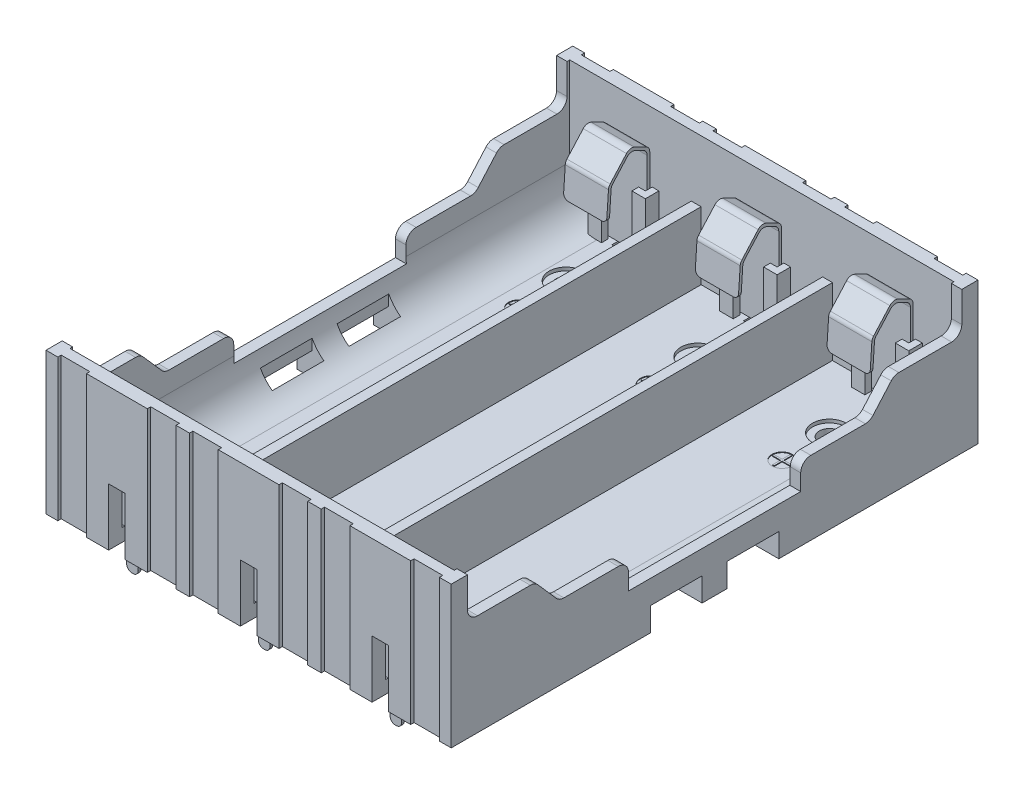
SolidWorks part; units mm, degrees
material "ABS"
ref_plane "Спереди" through (0, 0, 0) normal (0, 0, 1) x (1, 0, 0)
ref_plane "Сверху" through (0, 0, 0) normal (0, 1, 0) x (1, 0, 0)
ref_plane "Справа" through (0, 0, 0) normal (1, 0, 0) x (0, 0, -1)
other "Configuration Table"
sketch "Эскиз1" plane through (0, 0, 0) normal (0, 1, 0) x (1, 0, 0)
  line L1 (-30, 39) -> (30, 39)
  line L2 (-30, 39) -> (-30, -39)
  line L3 (-30, -39) -> (30, -39)
  line L4 (30, 39) -> (30, -39)
  line L5 (-30, 39) -> (30, -39) construction
  line L6 (-30, -39) -> (30, 39) construction
  point P0 (0, 0)
  dimension "D1" = 78
  dimension "D2" = 60
extrude "Основа" add sketch "Эскиз1" along normal blind 21
sketch "Эскиз2" plane through (0, 0, 0) normal (0, 1, 0) x (1, 0, 0)
  line L1 (30, 39) -> (-30, 39) construction
  line L2 (-4.5, 39) -> (-4.5, 38.5)
  line L3 (-4.5, 38.5) -> (-8.75, 38.5)
  line L4 (-8.75, 38.5) -> (-8.75, 39)
  line L5 (-8.75, 39) -> (-10.75, 39)
  line L6 (-10.75, 39) -> (-10.75, 38.5)
  line L7 (-10.75, 38.5) -> (-15, 38.5)
  line L8 (-15, 38.5) -> (-15, 39)
  line L9 (-15, 39) -> (-24, 39)
  line L10 (-24, 39) -> (-24, 38.5)
  line L11 (-24, 38.5) -> (-28.25, 38.5)
  line L12 (-28.25, 38.5) -> (-28.25, 39)
  line L13 (-28.25, 39) -> (-30, 39)
  line L14 (-30, 39) -> (-30, 49.7572)
  line L15 (-30, 49.7572) -> (30, 49.7572)
  line L16 (0, 49.7572) -> (0, 39)
  line L17 (4.5, 39) -> (-4.5, 39)
  line L18 (30, 39) -> (30, 49.7572)
  line L19 (15, 39) -> (24, 39)
  line L20 (24, 39) -> (24, 38.5)
  line L21 (28.25, 38.5) -> (28.25, 39)
  line L22 (24, 38.5) -> (28.25, 38.5)
  line L23 (28.25, 39) -> (30, 39)
  line L24 (15, 38.5) -> (15, 39)
  line L25 (10.75, 38.5) -> (15, 38.5)
  line L26 (10.75, 39) -> (10.75, 38.5)
  line L27 (8.75, 39) -> (10.75, 39)
  line L28 (4.5, 39) -> (4.5, 38.5)
  line L29 (4.5, 38.5) -> (8.75, 38.5)
  line L30 (8.75, 38.5) -> (8.75, 39)
  point P22 (0, 39)
  dimension "D1" = 9
  dimension "D2" = 2
  dimension "D3" = 4.25
  dimension "D4" = 0.5
extrude "Рёбра" cut sketch "Эскиз2" along normal through all contours L29 L30 L27 L26 L25 L24 L19 L20 L22 L21 L23 L18 L15 L16 L17 L28 | L17 L16 L15 L14 L13 L12 L11 L10 L9 L8 L7 L6 L5 L4 L3 L2 region at (-15.004, 0, -44.2695) region at (15.004, 0, -44.2695)
mirror "Зеркальное отражение1" about plane through (0, 0, 0) normal (0, 0, 1) of "Рёбра"
sketch "Эскиз3" plane through (0, 21, 0) normal (0, 1, 0) x (1, 0, 0)
  line L0 (19.45, 0) -> (-19.45, 0) construction
  line L1 (9, 37) -> (-9, 37)
  line L2 (9, 37) -> (9, -37)
  line L3 (9, -37) -> (-9, -37)
  line L4 (-9, 37) -> (-9, -37)
  line L5 (9, 37) -> (-9, -37) construction
  line L6 (9, -37) -> (-9, 37) construction
  line L8 (-28.45, 37) -> (-10.45, 37)
  line L9 (-28.45, 37) -> (-28.45, -37)
  line L10 (-28.45, -37) -> (-10.45, -37)
  line L11 (-10.45, 37) -> (-10.45, -37)
  line L12 (-28.45, 37) -> (-10.45, -37) construction
  line L13 (-28.45, -37) -> (-10.45, 37) construction
  line L15 (28.45, 37) -> (10.45, 37)
  line L16 (28.45, 37) -> (28.45, -37)
  line L17 (28.45, -37) -> (10.45, -37)
  line L18 (10.45, 37) -> (10.45, -37)
  line L19 (28.45, 37) -> (10.45, -37) construction
  line L20 (28.45, -37) -> (10.45, 37) construction
  point P0 (0, 0)
  point P9 (0, 0)
  dimension "D1" = 18
  dimension "D2" = 74
  dimension "D3" = 1.45
extrude "Отсеки" cut sketch "Эскиз3" against normal blind 19.1
fillet "Скругление1" radius 6 2 edges at (28.45, 1.9, 0) (-28.45, 1.9, 0)
sketch "Эскиз4" plane through (0, 0, 0) normal (1, 0, 0) x (0, 0, -1)
  line L0 (37, 21) -> (-37, 21) construction
  line L1 (37, 30.1) -> (-37, 30.1)
  line L2 (37, 30.1) -> (37, 11.9)
  line L3 (37, 11.9) -> (-37, 11.9)
  line L4 (-37, 30.1) -> (-37, 11.9)
  line L5 (37, 30.1) -> (-37, 11.9) construction
  line L6 (37, 11.9) -> (-37, 30.1) construction
  line L7 (-37, 1.9) -> (-37, 21) construction
  line L8 (37, 1.9) -> (-37, 1.9) construction
  point P0 (0, 21)
  dimension "D1" = 10
extrude "Уменьшение внутренних стенок" cut sketch "Эскиз4" against normal blind 15 and the other way blind 15
sketch "Эскиз5" plane through (30, 0, 0) normal (1, 0, 0) x (0, 0, -1)
  line L0 (-39, 21) -> (-36.6, 21)
  line L1 (-39, 21) -> (39, 21) construction
  line L2 (-36.6, 21) -> (-36.6, 15)
  line L3 (-36.6, 15) -> (-26.6, 15)
  line L4 (-26.6, 15) -> (-23, 10.9)
  line L5 (-23, 10.9) -> (-12.75, 10.9)
  line L6 (-12.75, 10.9) -> (-12.75, 7)
  line L7 (-12.75, 7) -> (12.75, 7)
  line L8 (0, 7) -> (0, 0) construction
  line L9 (-36.6, 21) -> (36.6, 21)
  line L10 (12.75, 10.9) -> (12.75, 7)
  line L11 (23, 10.9) -> (12.75, 10.9)
  line L12 (26.6, 15) -> (23, 10.9)
  line L13 (36.6, 15) -> (26.6, 15)
  line L14 (36.6, 21) -> (36.6, 15)
  point P20 (0, 21)
  line M12 (39, 21) -> (-39, 21)
  dimension "D1" = 12.75
  dimension "D2" = 10.25
  dimension "D3" = 2.4
  dimension "D4" = 10
  dimension "D5" = 6
  dimension "D6" = 3.9
  dimension "D7" = 7
extrude "Уменьшение внешних стенок" cut sketch "Эскиз5" against normal blind 15 contours L14 L2 L3 L4 L5 L6 L7 L10 L11 L12 L13 M12 region at (30, 15.4166, 0)
fillet "Скругление2" radius 1.5 8 edges at (29.225, 15, -36.6) (29.225, 15, -26.6) (29.225, 10.9, -23) (29.225, 10.9, -12.75) (29.225, 10.9, 12.75) (29.225, 10.9, 23) (29.225, 15, 26.6) (29.225, 15, 36.6)
mirror "Зеркальное отражение2" about plane through (0, 0, 0) normal (1, 0, 0) of "Скругление2", "Уменьшение внешних стенок"
sketch "Эскиз6" plane through (0, 0, 0) normal (0, 1, 0) x (1, 0, 0)
  line L0 (-4.5, -39) -> (4.5, -39) construction
  line L1 (-1.225, -42.5) -> (1.225, -42.5)
  line L2 (-1.225, -42.5) -> (-1.225, -35.5)
  line L3 (-1.225, -35.5) -> (1.225, -35.5)
  line L4 (1.225, -42.5) -> (1.225, -35.5)
  line L5 (-1.225, -42.5) -> (1.225, -35.5) construction
  line L6 (-1.225, -35.5) -> (1.225, -42.5) construction
  line L7 (-30, 0) -> (30, 0) construction
  line L8 (30, -39) -> (30, 39) construction
  line L9 (-24, -39) -> (-15, -39) construction
  line L10 (-20.725, -42.5) -> (-18.275, -42.5)
  line L11 (-20.725, -42.5) -> (-20.725, -35.5)
  line L12 (-20.725, -35.5) -> (-18.275, -35.5)
  line L13 (-18.275, -42.5) -> (-18.275, -35.5)
  line L14 (-20.725, -42.5) -> (-18.275, -35.5) construction
  line L15 (-20.725, -35.5) -> (-18.275, -42.5) construction
  line L16 (15, -39) -> (24, -39) construction
  line L17 (20.725, -42.5) -> (18.275, -42.5)
  line L18 (20.725, -42.5) -> (20.725, -35.5)
  line L19 (20.725, -35.5) -> (18.275, -35.5)
  line L20 (18.275, -42.5) -> (18.275, -35.5)
  line L21 (20.725, -42.5) -> (18.275, -35.5) construction
  line L22 (20.725, -35.5) -> (18.275, -42.5) construction
  line L23 (20.725, 35.5) -> (18.275, 42.5) construction
  line L24 (20.725, 42.5) -> (18.275, 35.5) construction
  line L25 (-20.725, 35.5) -> (-18.275, 42.5) construction
  line L26 (-20.725, 42.5) -> (-18.275, 35.5) construction
  line L27 (-1.225, 35.5) -> (1.225, 42.5) construction
  line L28 (-1.225, 42.5) -> (1.225, 35.5) construction
  line L29 (18.275, 42.5) -> (18.275, 35.5)
  line L30 (20.725, 35.5) -> (18.275, 35.5)
  line L31 (20.725, 42.5) -> (20.725, 35.5)
  line L32 (20.725, 42.5) -> (18.275, 42.5)
  line L33 (-18.275, 42.5) -> (-18.275, 35.5)
  line L34 (-20.725, 35.5) -> (-18.275, 35.5)
  line L35 (-20.725, 42.5) -> (-20.725, 35.5)
  line L36 (-20.725, 42.5) -> (-18.275, 42.5)
  line L37 (1.225, 42.5) -> (1.225, 35.5)
  line L38 (-1.225, 35.5) -> (1.225, 35.5)
  line L39 (-1.225, 42.5) -> (-1.225, 35.5)
  line L40 (-1.225, 42.5) -> (1.225, 42.5)
  point P0 (0, -39)
  point P7 (-19.5, -39)
  point P13 (0, 0)
  point P21 (19.5, -39)
  point P40 (19.5, 39)
  point P41 (-19.5, 39)
  point P42 (0, 39)
  dimension "D1" = 2.45
  dimension "D2" = 3.5
extrude "Вырезы под контакты" cut sketch "Эскиз6" along normal blind 8.5
sketch "Эскиз7" plane through (0, 0, 0) normal (0, 1, 0) x (1, 0, 0)
  line L0 (0, -35.5) -> (0, 35.5) construction
  line L1 (1.225, -35.5) -> (-1.225, -35.5) construction
  line L2 (-1.225, 35.5) -> (1.225, 35.5) construction
  line L3 (0, 0) -> (-26.025, 0) construction
  line L4 (-26.025, -23.825) -> (-26.025, 23.825) construction
  line L5 (-24, -38.5) -> (-28.25, -38.5) construction
  line L6 (-24.325, -10.8) -> (-27.725, -10.8)
  line L7 (-24.325, -10.8) -> (-24.325, -36.85)
  line L8 (-24.325, -36.85) -> (-27.725, -36.85)
  line L9 (-27.725, -10.8) -> (-27.725, -36.85)
  line L10 (-24.325, -10.8) -> (-27.725, -36.85) construction
  line L11 (-24.325, -36.85) -> (-27.725, -10.8) construction
  line L12 (-24.325, 10.8) -> (-27.725, 10.8)
  line L13 (-24.325, 10.8) -> (-24.325, 36.85)
  line L14 (-24.325, 36.85) -> (-27.725, 36.85)
  line L15 (-27.725, 10.8) -> (-27.725, 36.85)
  line L16 (-24.325, 10.8) -> (-27.725, 36.85) construction
  line L17 (-24.325, 36.85) -> (-27.725, 10.8) construction
  line L18 (-27.725, -1.375) -> (-24.325, -1.375)
  line L19 (-27.725, -1.375) -> (-27.725, 1.375)
  line L20 (-27.725, 1.375) -> (-24.325, 1.375)
  line L21 (-24.325, -1.375) -> (-24.325, 1.375)
  line L22 (-27.725, -1.375) -> (-24.325, 1.375) construction
  line L23 (-27.725, 1.375) -> (-24.325, -1.375) construction
  line L24 (24.325, 36.85) -> (27.725, 36.85)
  line L25 (24.325, 10.8) -> (24.325, 36.85)
  line L26 (27.725, 10.8) -> (27.725, 36.85)
  line L27 (24.325, 10.8) -> (27.725, 10.8)
  line L28 (24.325, -10.8) -> (27.725, -10.8)
  line L29 (24.325, -10.8) -> (24.325, -36.85)
  line L30 (27.725, -10.8) -> (27.725, -36.85)
  line L31 (24.325, -36.85) -> (27.725, -36.85)
  line L32 (27.725, -1.375) -> (27.725, 1.375)
  line L33 (27.725, -1.375) -> (24.325, -1.375)
  line L34 (24.325, -1.375) -> (24.325, 1.375)
  line L35 (27.725, 1.375) -> (24.325, 1.375)
  point P11 (-26.025, 0)
  dimension "D1" = 21.6
  dimension "D2" = 3.4
  dimension "D3" = 2.75
  dimension "D4" = 24.325
  dimension "D5" = 1.65
extrude "Пазы снизу" cut sketch "Эскиз7" along normal blind 1
sketch "Эскиз8" plane through (0, 0, 0) normal (0, 0, 1) x (1, 0, 0)
  line L0 (24.325, 1) -> (27.725, 1)
  line L1 (27.725, 1) -> (27.725, 3.073)
  arc A0 (24.325, 1) -> (27.725, 3.073) centre (22.45, 7.9) ccw
  arc A1 (22.45, 1.9) -> (28.45, 7.9) centre (22.45, 7.9) ccw construction
  arc A2 (22.45, 1.9) -> (28.45, 7.9) centre (22.45, 7.9) ccw construction
extrude "Вырез-Вытянуть9" cut sketch "Эскиз8" against normal up to surface and the other way up to surface up to face at (26.025, 0.5, -1.375) other way up to face at (26.025, 0.5, 1.375)
extrude "Вырез-Вытянуть10" cut sketch "Эскиз8<3>" along direction (0, 0, 1) on the side against the normal up to surface (36.85 mm away) from surface contours A0 L0 L1 region at (26.7298, 1.6233, 0) up to face at (26.025, 0.5, -36.85) starting at face at (26.025, 0.5, -10.8)
sketch "Эскиз8<3>" plane through (0, 0, 0) normal (0, 0, 1) x (1, 0, 0) same geometry as "Эскиз8"
extrude "Вырез-Вытянуть11" cut sketch "Эскиз8<4>" along normal up to surface (36.85 mm away) from surface up to face at (26.025, 0.5, 36.85) starting at face at (26.025, 0.5, 10.8)
sketch "Эскиз8<4>" plane through (0, 0, 0) normal (0, 0, 1) x (1, 0, 0) same geometry as "Эскиз8"
mirror "Зеркальное отражение3" about plane through (0, 0, 0) normal (1, 0, 0) of "Вырез-Вытянуть11", "Вырез-Вытянуть10", "Вырез-Вытянуть9"
sketch "Эскиз9" plane through (0, 0, 0) normal (0, 1, 0) x (1, 0, 0)
  line L0 (-30, 39) -> (-30, -39) construction
  line L1 (-34, -9.5) -> (-26, -9.5)
  line L2 (-34, -9.5) -> (-34, -1.85)
  line L3 (-34, -1.85) -> (-26, -1.85)
  line L4 (-26, -9.5) -> (-26, -1.85)
  line L5 (-34, -9.5) -> (-26, -1.85) construction
  line L6 (-34, -1.85) -> (-26, -9.5) construction
  line L7 (0, 0) -> (-30, 0) construction
  line L8 (-34, 1.85) -> (-26, 1.85)
  line L9 (-34, 1.85) -> (-34, 9.5)
  line L10 (-34, 9.5) -> (-26, 9.5)
  line L11 (-26, 1.85) -> (-26, 9.5)
  line L12 (-34, 1.85) -> (-26, 9.5) construction
  line L13 (-34, 9.5) -> (-26, 1.85) construction
  line L14 (-30, 0) -> (-30, 5.675) construction
  line L15 (-30, 0) -> (-30, -5.675) construction
  line L16 (0, 0) -> (0, -8.7492) construction
  line L17 (30, 0) -> (30, -5.675) construction
  line L18 (30, 0) -> (30, 5.675) construction
  line L19 (34, 9.5) -> (26, 1.85) construction
  line L20 (34, 1.85) -> (26, 9.5) construction
  line L21 (34, -1.85) -> (26, -9.5) construction
  line L22 (34, -9.5) -> (26, -1.85) construction
  line L23 (26, 1.85) -> (26, 9.5)
  line L24 (34, 9.5) -> (26, 9.5)
  line L25 (34, 1.85) -> (34, 9.5)
  line L26 (34, 1.85) -> (26, 1.85)
  line L27 (26, -9.5) -> (26, -1.85)
  line L28 (34, -1.85) -> (26, -1.85)
  line L29 (34, -9.5) -> (34, -1.85)
  line L30 (34, -9.5) -> (26, -9.5)
  point P0 (-30, -5.675)
  point P7 (-30, 5.675)
  point P29 (30, 5.675)
  point P30 (30, -5.675)
  dimension "D1" = 7.65
  dimension "D2" = 4
  dimension "D3" = 3.7
extrude "Пазы сбоку" cut sketch "Эскиз9" along normal blind 3.5
sketch "Эскиз10" plane through (0, 0, 0) normal (0, 1, 0) x (1, 0, 0)
  line L2 (-26, -9.5) -> (-26, -1.85) construction
  line L3 (-26, 1.85) -> (-26, 9.5) construction
  line L4 (0, 0) -> (0, -13.336) construction
  line L5 (27.75, 1.85) -> (26, 1.85)
  line L6 (-26, -9.5) -> (-26, -1.85)
  line L7 (-26, 1.85) -> (-26, 9.5)
  line L8 (-26, -1.85) -> (-27.75, -1.85)
  line L9 (-26, -1.85) -> (-30, -1.85) construction
  line L10 (-27.75, -1.85) -> (-27.75, -9.5)
  line L11 (-30, -9.5) -> (-26, -9.5) construction
  line L12 (-27.75, -9.5) -> (-26, -9.5)
  line L13 (-26, 9.5) -> (-27.75, 9.5)
  line L14 (-26.5292, 9.5) -> (-30, 9.5) construction
  line L15 (-27.75, 9.5) -> (-27.75, 1.85)
  line L16 (-30, 1.85) -> (-26, 1.85) construction
  line L17 (-27.75, 1.85) -> (-26, 1.85)
  line L18 (27.75, 9.5) -> (27.75, 1.85)
  line L19 (26, 9.5) -> (27.75, 9.5)
  line L20 (27.75, -9.5) -> (26, -9.5)
  line L21 (27.75, -1.85) -> (27.75, -9.5)
  line L22 (26, -1.85) -> (27.75, -1.85)
  line L23 (26, 1.85) -> (26, 9.5)
  line L24 (26, -9.5) -> (26, -1.85)
  dimension "D1" = 1.75
extrude "Вырез-Вытянуть15" cut sketch "Эскиз10" along normal through all
sketch "Эскиз11" plane through (0, 0, 0) normal (0, 1, 0) x (1, 0, 0)
  line L0 (-19.5, 35.5) -> (-19.5, 27.5) construction
  line L1 (19.5, -27.5) -> (-19.5, -27.5) construction
  line L2 (19.5, -27.5) -> (19.5, 27.5) construction
  line L3 (19.5, 27.5) -> (-19.5, 27.5) construction
  line L4 (-19.5, -27.5) -> (-19.5, 27.5) construction
  line L5 (19.5, -27.5) -> (-19.5, 27.5) construction
  line L6 (19.5, 27.5) -> (-19.5, -27.5) construction
  line L7 (-18.275, 35.5) -> (-20.725, 35.5) construction
  circle A0 centre (-19.5, 27.5) radius 1.5
  circle A1 centre (0, 27.5) radius 1.5
  circle A2 centre (19.5, 27.5) radius 1.5
  circle A3 centre (19.5, -27.5) radius 1.5
  circle A4 centre (0, -27.5) radius 1.5
  circle A5 centre (-19.5, -27.5) radius 1.5
  point P0 (0, 0)
  dimension "D2" = 3
  dimension "D1" = 55
extrude "Крепежные отверстия" cut sketch "Эскиз11" along normal through all
sketch "Эскиз12" plane through (0, 0, 0) normal (0, 1, 0) x (1, 0, 0)
  circle A0 centre (-19.5, 27.5) radius 1.5 construction
  circle A1 centre (0, 27.5) radius 1.5 construction
  circle A2 centre (19.5, 27.5) radius 1.5 construction
  circle A3 centre (19.5, -27.5) radius 1.5 construction
  circle A4 centre (0, -27.5) radius 1.5 construction
  circle A5 centre (-19.5, -27.5) radius 1.5 construction
  circle A6 centre (-19.5, 27.5) radius 1.5
  circle A7 centre (0, 27.5) radius 1.5
  circle A8 centre (19.5, 27.5) radius 1.5
  circle A9 centre (19.5, -27.5) radius 1.5
  circle A10 centre (0, -27.5) radius 1.5
  circle A11 centre (-19.5, -27.5) radius 1.5
  circle A12 centre (-19.5, 27.5) radius 2.8
  circle A13 centre (0, 27.5) radius 2.8
  circle A14 centre (19.5, 27.5) radius 2.8
  circle A15 centre (19.5, -27.5) radius 2.8
  circle A16 centre (0, -27.5) radius 2.8
  circle A17 centre (-19.5, -27.5) radius 2.8
  dimension "D1" = 1.3
extrude "Юбки отверстий" add sketch "Эскиз12" against normal blind 0.3
sketch "Эскиз13" plane through (0, 1.9, 0) normal (0, 1, 0) x (1, 0, 0)
  circle A0 centre (-19.5, -27.5) radius 1.5 construction
  circle A1 centre (0, -27.5) radius 1.5 construction
  circle A2 centre (19.5, 27.5) radius 1.5 construction
  circle A3 centre (0, 27.5) radius 1.5 construction
  circle A4 centre (-19.5, 27.5) radius 1.5 construction
  circle A5 centre (-19.5, -27.5) radius 1.5
  circle A6 centre (0, -27.5) radius 1.5
  circle A7 centre (19.5, 27.5) radius 1.5
  circle A8 centre (0, 27.5) radius 1.5
  circle A9 centre (-19.5, 27.5) radius 1.5
  circle A10 centre (19.5, -27.5) radius 1.5 construction
  circle A11 centre (19.5, -27.5) radius 1.5
  circle A12 centre (-19.5, -27.5) radius 2.5
  circle A13 centre (0, -27.5) radius 2.5
  circle A14 centre (19.5, 27.5) radius 2.5
  circle A15 centre (0, 27.5) radius 2.5
  circle A16 centre (-19.5, 27.5) radius 2.5
  circle A17 centre (19.5, -27.5) radius 2.5
  dimension "D1" = 1
extrude "Вырез-Вытянуть17" cut sketch "Эскиз13" against normal blind 0.5
sketch "Эскиз14" plane through (0, 1.9, 0) normal (0, 1, 0) x (1, 0, 0)
  line L0 (-19.5, 20.5) -> (-19.5, 27.5) construction
  line L1 (19.5, -20.5) -> (-19.5, -20.5) construction
  line L2 (19.5, -20.5) -> (19.5, 20.5) construction
  line L3 (19.5, 20.5) -> (-19.5, 20.5) construction
  line L4 (-19.5, -20.5) -> (-19.5, 20.5) construction
  line L5 (19.5, -20.5) -> (-19.5, 20.5) construction
  line L6 (19.5, 20.5) -> (-19.5, -20.5) construction
  line L7 (0.125, -19.2) -> (-0.125, -19.2)
  line L8 (-19.375, -19.2) -> (-19.625, -19.2)
  line L9 (-19.375, -19.2) -> (-19.375, -21.8)
  line L10 (-19.375, -21.8) -> (-19.625, -21.8)
  line L11 (-19.625, -19.2) -> (-19.625, -21.8)
  line L12 (-19.375, -19.2) -> (-19.625, -21.8) construction
  line L13 (-19.375, -21.8) -> (-19.625, -19.2) construction
  line L14 (-19.375, 21.8) -> (-19.625, 21.8)
  line L15 (-19.375, 21.8) -> (-19.375, 19.2)
  line L16 (-19.375, 19.2) -> (-19.625, 19.2)
  line L17 (-19.625, 21.8) -> (-19.625, 19.2)
  line L18 (-19.375, 21.8) -> (-19.625, 19.2) construction
  line L19 (-19.375, 19.2) -> (-19.625, 21.8) construction
  line L20 (-18.2, 20.625) -> (-20.8, 20.625)
  line L21 (-18.2, 20.625) -> (-18.2, 20.375)
  line L22 (-18.2, 20.375) -> (-20.8, 20.375)
  line L23 (-20.8, 20.625) -> (-20.8, 20.375)
  line L24 (-18.2, 20.625) -> (-20.8, 20.375) construction
  line L25 (-18.2, 20.375) -> (-20.8, 20.625) construction
  line L26 (0.125, -19.2) -> (0.125, -21.8)
  line L27 (0.125, -21.8) -> (-0.125, -21.8)
  line L28 (-0.125, -19.2) -> (-0.125, -21.8)
  line L29 (0.125, 21.8) -> (-0.125, 21.8)
  line L30 (0.125, 21.8) -> (0.125, 19.2)
  line L31 (0.125, 19.2) -> (-0.125, 19.2)
  line L32 (-0.125, 21.8) -> (-0.125, 19.2)
  line L33 (1.3, 20.625) -> (-1.3, 20.625)
  line L34 (1.3, 20.625) -> (1.3, 20.375)
  line L35 (1.3, 20.375) -> (-1.3, 20.375)
  line L36 (-1.3, 20.625) -> (-1.3, 20.375)
  line L37 (0, -20.5) -> (0, 20.5) construction
  line L38 (0.125, -19.2) -> (-0.125, -21.8) construction
  line L39 (0.125, -21.8) -> (-0.125, -19.2) construction
  line L40 (0.125, 21.8) -> (-0.125, 19.2) construction
  line L41 (0.125, 19.2) -> (-0.125, 21.8) construction
  line L42 (1.3, 20.625) -> (-1.3, 20.375) construction
  line L43 (1.3, 20.375) -> (-1.3, 20.625) construction
  line L44 (19.625, -19.2) -> (19.375, -19.2)
  line L45 (19.625, -19.2) -> (19.625, -21.8)
  line L46 (19.625, -21.8) -> (19.375, -21.8)
  line L47 (19.375, -19.2) -> (19.375, -21.8)
  line L48 (19.625, 21.8) -> (19.375, 21.8)
  line L49 (19.625, 21.8) -> (19.625, 19.2)
  line L50 (19.625, 19.2) -> (19.375, 19.2)
  line L51 (19.375, 21.8) -> (19.375, 19.2)
  line L52 (20.8, 20.625) -> (18.2, 20.625)
  line L53 (20.8, 20.625) -> (20.8, 20.375)
  line L54 (20.8, 20.375) -> (18.2, 20.375)
  line L55 (18.2, 20.625) -> (18.2, 20.375)
  line L56 (19.5, -20.5) -> (19.5, 20.5) construction
  line L57 (19.625, -19.2) -> (19.375, -21.8) construction
  line L58 (19.625, -21.8) -> (19.375, -19.2) construction
  line L59 (19.625, 21.8) -> (19.375, 19.2) construction
  line L60 (19.625, 19.2) -> (19.375, 21.8) construction
  line L61 (20.8, 20.625) -> (18.2, 20.375) construction
  line L62 (20.8, 20.375) -> (18.2, 20.625) construction
  circle A0 centre (-19.5, 20.5) radius 1.5
  circle A1 centre (-19.5, -20.5) radius 1.5
  circle A2 centre (0, 20.5) radius 1.5
  circle A3 centre (0, -20.5) radius 1.5
  circle A4 centre (19.5, 20.5) radius 1.5
  circle A5 centre (19.5, -20.5) radius 1.5
  point P0 (0, 0)
  dimension "D2" = 3
  dimension "D1" = 7
  dimension "D3" = 2.6
  dimension "D4" = 0.25
  dimension "D5" = 3
extrude "Полярность" cut sketch "Эскиз14" against normal blind 0.1 contours A3 L28 L7 L26 L27 | A5 L47 L44 L45 L46 | A1 L11 L8 L9 L10 | A0 L23 L20 L17 L14 L15 L21 L22 L16 | A2 L36 L33 L32 L29 L30 L34 L35 L31 | A4 L55 L52 L51 L48 L49 L53 L54 L50 region at (-20.9576, 1.9, -20.5) region at (-20.9576, 1.9, 20.5) region at (-1.4576, 1.9, -20.5) region at (-1.4576, 1.9, 20.5) region at (18.0424, 1.9, -20.5) region at (18.0424, 1.9, 20.5)
sketch "Эскиз15" plane through (0, 1.9, 0) normal (0, 1, 0) x (1, 0, 0)
  line L0 (-19.5, 35.5) -> (-19.5, 35) construction
  line L1 (-18.275, 35.5) -> (-20.725, 35.5) construction
  line L2 (-21.75, 35) -> (-17.25, 35) construction
  line L3 (-21.75, 35) -> (-23.75, 35)
  line L4 (-23.75, 35) -> (-23.75, 37)
  line L5 (28.45, 37) -> (-28.45, 37) construction
  line L6 (-23.75, 37) -> (-22.75, 37)
  line L7 (-22.75, 37) -> (-22.75, 36)
  line L8 (-22.75, 36) -> (-21.75, 36)
  line L9 (-21.75, 36) -> (-21.75, 35)
  line L10 (-17.25, 35) -> (-17.25, 36)
  line L11 (-17.25, 36) -> (-16.25, 36)
  line L12 (-16.25, 36) -> (-16.25, 37)
  line L13 (-16.25, 37) -> (-15.25, 37)
  line L14 (-15.25, 37) -> (-15.25, 35)
  line L15 (-15.25, 35) -> (-17.25, 35)
  line L16 (-2.25, 35) -> (-4.25, 35)
  line L17 (-4.25, 35) -> (-4.25, 37)
  line L18 (-4.25, 37) -> (-3.25, 37)
  line L19 (-3.25, 37) -> (-3.25, 36)
  line L20 (-3.25, 36) -> (-2.25, 36)
  line L21 (-2.25, 36) -> (-2.25, 35)
  line L22 (2.25, 35) -> (2.25, 36)
  line L23 (2.25, 36) -> (3.25, 36)
  line L24 (3.25, 36) -> (3.25, 37)
  line L25 (3.25, 37) -> (4.25, 37)
  line L26 (4.25, 37) -> (4.25, 35)
  line L27 (4.25, 35) -> (2.25, 35)
  line L28 (0, 35.5) -> (0, 35) construction
  line L29 (-2.25, 35) -> (2.25, 35) construction
  line L30 (17.25, 35) -> (15.25, 35)
  line L31 (15.25, 35) -> (15.25, 37)
  line L32 (15.25, 37) -> (16.25, 37)
  line L33 (16.25, 37) -> (16.25, 36)
  line L34 (16.25, 36) -> (17.25, 36)
  line L35 (17.25, 36) -> (17.25, 35)
  line L36 (21.75, 35) -> (21.75, 36)
  line L37 (21.75, 36) -> (22.75, 36)
  line L38 (22.75, 36) -> (22.75, 37)
  line L39 (22.75, 37) -> (23.75, 37)
  line L40 (23.75, 37) -> (23.75, 35)
  line L41 (23.75, 35) -> (21.75, 35)
  line L42 (19.5, 35.5) -> (19.5, 35) construction
  line L43 (17.25, 35) -> (21.75, 35) construction
  line L44 (30, 0) -> (-30, 0) construction
  line L45 (-30, -12.75) -> (-30, 12.75) construction
  line L46 (17.25, -35) -> (21.75, -35) construction
  line L47 (19.5, -35.5) -> (19.5, -35) construction
  line L48 (-2.25, -35) -> (2.25, -35) construction
  line L49 (0, -35.5) -> (0, -35) construction
  line L50 (-21.75, -35) -> (-17.25, -35) construction
  line L51 (-19.5, -35.5) -> (-19.5, -35) construction
  line L52 (23.75, -35) -> (21.75, -35)
  line L53 (23.75, -37) -> (23.75, -35)
  line L54 (22.75, -37) -> (23.75, -37)
  line L55 (22.75, -36) -> (22.75, -37)
  line L56 (21.75, -36) -> (22.75, -36)
  line L57 (21.75, -35) -> (21.75, -36)
  line L58 (17.25, -36) -> (17.25, -35)
  line L59 (16.25, -36) -> (17.25, -36)
  line L60 (16.25, -37) -> (16.25, -36)
  line L61 (15.25, -37) -> (16.25, -37)
  line L62 (15.25, -35) -> (15.25, -37)
  line L63 (17.25, -35) -> (15.25, -35)
  line L64 (4.25, -35) -> (2.25, -35)
  line L65 (4.25, -37) -> (4.25, -35)
  line L66 (3.25, -37) -> (4.25, -37)
  line L67 (3.25, -36) -> (3.25, -37)
  line L68 (2.25, -36) -> (3.25, -36)
  line L69 (2.25, -35) -> (2.25, -36)
  line L70 (-2.25, -36) -> (-2.25, -35)
  line L71 (-3.25, -36) -> (-2.25, -36)
  line L72 (-3.25, -37) -> (-3.25, -36)
  line L73 (-4.25, -37) -> (-3.25, -37)
  line L74 (-4.25, -35) -> (-4.25, -37)
  line L75 (-2.25, -35) -> (-4.25, -35)
  line L76 (-15.25, -35) -> (-17.25, -35)
  line L77 (-15.25, -37) -> (-15.25, -35)
  line L78 (-16.25, -37) -> (-15.25, -37)
  line L79 (-16.25, -36) -> (-16.25, -37)
  line L80 (-17.25, -36) -> (-16.25, -36)
  line L81 (-17.25, -35) -> (-17.25, -36)
  line L82 (-21.75, -36) -> (-21.75, -35)
  line L83 (-22.75, -36) -> (-21.75, -36)
  line L84 (-22.75, -37) -> (-22.75, -36)
  line L85 (-23.75, -37) -> (-22.75, -37)
  line L86 (-23.75, -35) -> (-23.75, -37)
  line L87 (-21.75, -35) -> (-23.75, -35)
  point P7 (-19.5, 35)
  point P24 (0, 35)
  point P39 (19.5, 35)
  point P55 (0, 0)
  point P98 (19.5, -35)
  point P99 (0, -35)
  point P100 (-19.5, -35)
  dimension "D1" = 2
  dimension "D2" = 1
  dimension "D3" = 8.5
  dimension "D4" = 2
  dimension "D5" = 3
extrude "Пазы для контактов" add sketch "Эскиз15" along normal blind 8.9
ref_plane "Для эскиза контактов" through (-19.5, 0, 0) normal (-1, 0, 0) x (0, 0, 1)
sketch "Эскиз16" plane through (-19.5, 0, 0) normal (-1, 0, 0) x (0, 0, 1)
  line L0 (-37, 6.35) -> (-36, 6.35) construction
  line L1 (-37, 10.8) -> (-37, 1.9) construction
  line L2 (-36, 10.8) -> (-36, 1.9) construction
  line L3 (-36.5, 17.26) -> (-36.5, 15.9523) construction
  line L4 (-36.5, 15.9523) -> (-33.8, 17.26)
  line L5 (-33.8, 17.26) -> (-30.8, 13.9059)
  line L6 (-30.8, 13.9059) -> (-30.5, 9.4159)
  line L7 (-36.5, 17.26) -> (-33.8, 17.26) construction
  line L8 (-36.5, 15.9523) -> (-36.5, 2)
  line L9 (-35.5, 0) -> (-39, 0) construction
  line L10 (-36.5, 2) -> (-36.5, -3.54) construction
  line L11 (-37, 1.9) -> (-35.5, 1.9) construction
  point P17 (-36.5, 6.35)
  dimension "D1" = 20.8
  dimension "D2" = 3
  dimension "D3" = 4.5
  dimension "D4" = 6
  dimension "D5" = 5.7
  dimension "D6" = 2.7
  dimension "D7" = 3.54
  dimension "D8" = 0.1
extrude "Контакт" add sketch "Эскиз16" along normal mid plane 6.4 thin thin type mid plane wall 0.4
sketch "Эскиз17" plane through (0, 2, 0) normal (0, -1, 0) x (1, 0, 0)
  line L0 (-19.5, -36.7) -> (-19.5, -36.3) construction
  line L1 (-22.7, -36.7) -> (-16.3, -36.7) construction
  line L2 (-22.7, -36.3) -> (-16.3, -36.3) construction
  line L4 (-18.65, -36.3) -> (-20.35, -36.3)
  line L5 (-18.65, -36.3) -> (-18.65, -36.7)
  line L6 (-18.65, -36.7) -> (-20.35, -36.7)
  line L7 (-20.35, -36.3) -> (-20.35, -36.7)
  line L8 (-18.65, -36.3) -> (-20.35, -36.7) construction
  line L9 (-18.65, -36.7) -> (-20.35, -36.3) construction
  point P6 (-19.5, -36.5)
  dimension "D1" = 1.7
extrude "Штырёк для пайки" add sketch "Эскиз17" along normal blind 5.5
fillet "Скругление3" radius 1 6 edges at (-19.5, 13.8239, -30.995) (-19.5, 13.9879, -30.605) (-19.5, 17.0143, -33.8485) (-19.5, 17.5057, -33.7515) (-19.5, 15.827, -36.3) (-19.5, 16.0777, -36.7)
fillet "Скругление4" radius 0.75 6 edges at (-16.3, 2, -36.5) (-18.65, -3.5, -36.5) (-20.35, -3.5, -36.5) (-22.7, 2, -36.5) (-16.3, 9.4159, -30.5) (-22.7, 9.4159, -30.5)
pattern_linear "Линейный массив1" count 3 spacing 19.5 along (1, 0, 0) of bodies 125
mirror "Зеркальное отражение4" about plane through (0, 0, 0) normal (0, 0, 1) of bodies 127 126 125
equation "\"D1@Эскиз5\"=25.5/2"
equation "\"D4@Эскиз7\"=48.65/2"
